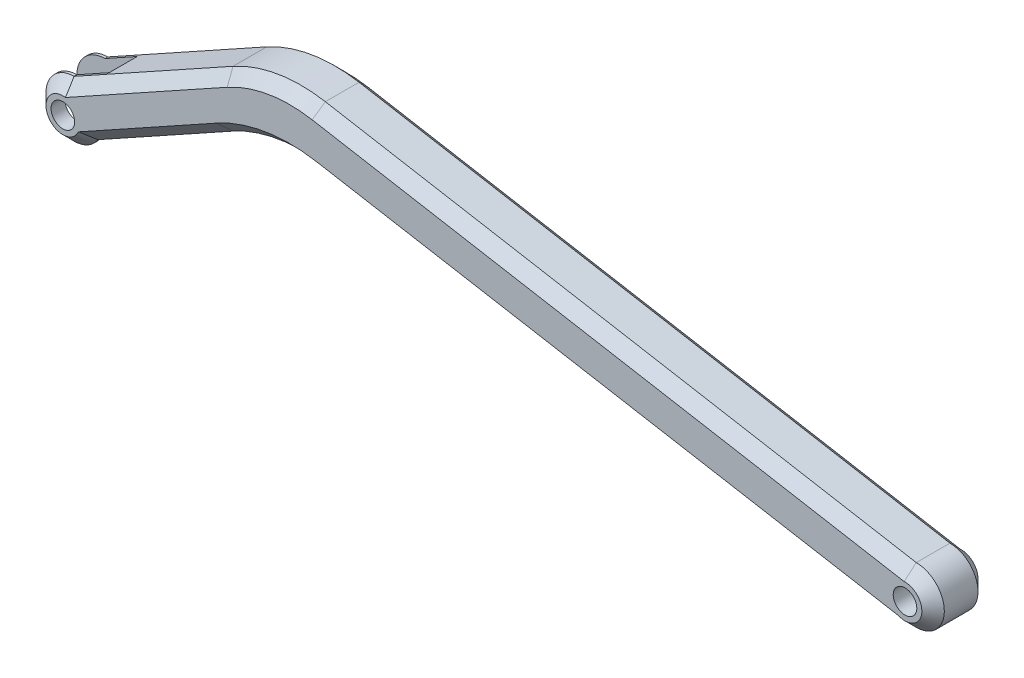
SolidWorks part; units mm, degrees
ref_plane "Front Plane" through (0, 0, 0) normal (0, 0, 1) x (1, 0, 0)
ref_plane "Top Plane" through (0, 0, 0) normal (0, 1, 0) x (1, 0, 0)
ref_plane "Right Plane" through (0, 0, 0) normal (1, 0, 0) x (0, 0, -1)
sketch "Sketch1" plane through (0, 0, 0) normal (0, 0, 1) x (1, 0, 0)
  line L0 (-75, 0) -> (75, 0)
  line L1 (-75, 5) -> (-46.6923, 20.7072)
  line L2 (-75, 0) -> (-46.6923, 15.7072)
  line L3 (75, 0) -> (-30.241, 18.4705)
  line L4 (75, 5) -> (-30.241, 23.4705)
  line L5 (-70.7575, -2.6459) -> (-46.6923, 10.7072)
  line L6 (73.2974, -4.7012) -> (-30.241, 13.4705)
  circle A0 centre (-75, 0) radius 5
  circle A1 centre (75, 0) radius 5
  arc A2 (-30.241, 18.4705) -> (-46.6923, 15.7072) centre (-34.5626, -6.1531) ccw
  arc A3 (-30.241, 23.4705) -> (-46.6923, 20.7072) centre (-34.5626, -1.1531) ccw
  arc A4 (-30.241, 13.4705) -> (-46.6923, 10.7072) centre (-34.5626, -11.1531) ccw
  point P4 (0, 0)
  dimension "D1" = 25
  dimension "D2" = 2
  dimension "D3" = 2
extrude "Boss-Extrude2" add sketch "Sketch1" along normal mid plane 10 contours L2 A0 L0 | L4 A3 L1 A0 L2 A2 L3 A1 | A4 L6 L0 A1 L3 A2 L2 A0 L5 | A1 L3 L0 | A1 L0 L6 | A0 L5 L0 | L0 A0 L2 | L3 A1 L0 region at (-71.8074, 0.8264, 0) region at (-75.28, -0.0725, 0) region at (-68.7852, 1.6087, 0) region at (-68.8157, -0.8488, 0) region at (-71.6933, 5.6164, 0) region at (62.7162, -1.499, 0) region at (71.6834, 0.2888, 0) region at (75.0943, -0.0082, 0)
chamfer "Chamfer2" distance 2 angle 45 8 edges at (-79.3721, -2.4259, -5) (-60.8461, 12.8536, -5) (-38.7039, 23.5015, -5) (22.3795, 14.2353, -5) (79.9247, -0.8643, -5) (21.5282, 4.3847, -5) (-38.7039, 13.5015, -5) (-58.7249, 4.0306, -5)
ref_axis "Axis1" through (-75, 0, 8.351) along (0, 0, -1)
ref_axis "Axis2" through (75, 0, 27.342) along (0, 0, -1)
sketch "Sketch3" plane through (-19.7767, 35.6419, 0) normal (-0.4852, 0.8744, 0) x (0.8744, 0.4852, 0)
  line L0 (-65.5808, 3.1257) -> (-65.5808, -3.1257)
  line L3 (-65.5808, -8.351) -> (-65.5808, 11.0356) construction
  line L4 (-74.5808, 2.5) -> (-56.5808, 2.5)
  line L5 (-74.5808, 2.5) -> (-74.5808, -2.5)
  line L6 (-74.5808, -2.5) -> (-56.5808, -2.5)
  line L7 (-56.5808, 2.5) -> (-56.5808, -2.5)
  line L8 (-74.5808, 2.5) -> (-56.5808, -2.5) construction
  line L9 (-74.5808, -2.5) -> (-56.5808, 2.5) construction
  point P4 (-65.5808, 0)
  point P8 (-65.5808, 0)
  line M7 (-63.1549, 3) -> (-63.1549, -5)
extrude "Cut-Extrude2" cut sketch "Sketch3" against normal blind 14 and the other way blind 4 contours L5 L6 L0 L4 | L7 L4 L6 M7 | L0 L6 L4 M7 region at (-76.0606, 4.4115, 0) region at (-81.0561, 1.6396, 0) region at (-72.1258, 6.5948, 0)
sketch "Sketch4" plane through (0, 0, 5) normal (0, 0, 1) x (1, 0, 0)
  circle A0 centre (-75, 0) radius 2.1
  circle A1 centre (75, 0) radius 2.1
extrude "Cut-Extrude3" cut sketch "Sketch4" against normal through all
chamfer "Chamfer3" distance 2 angle 45 8 edges at (79.9247, -0.8643, 5) (21.5282, 4.3847, 5) (-38.7039, 13.5015, 5) (-58.7249, 4.0306, 5) (-79.3721, -2.4259, 5) (-60.8461, 12.8536, 5) (-38.7039, 23.5015, 5) (22.3795, 14.2353, 5)
